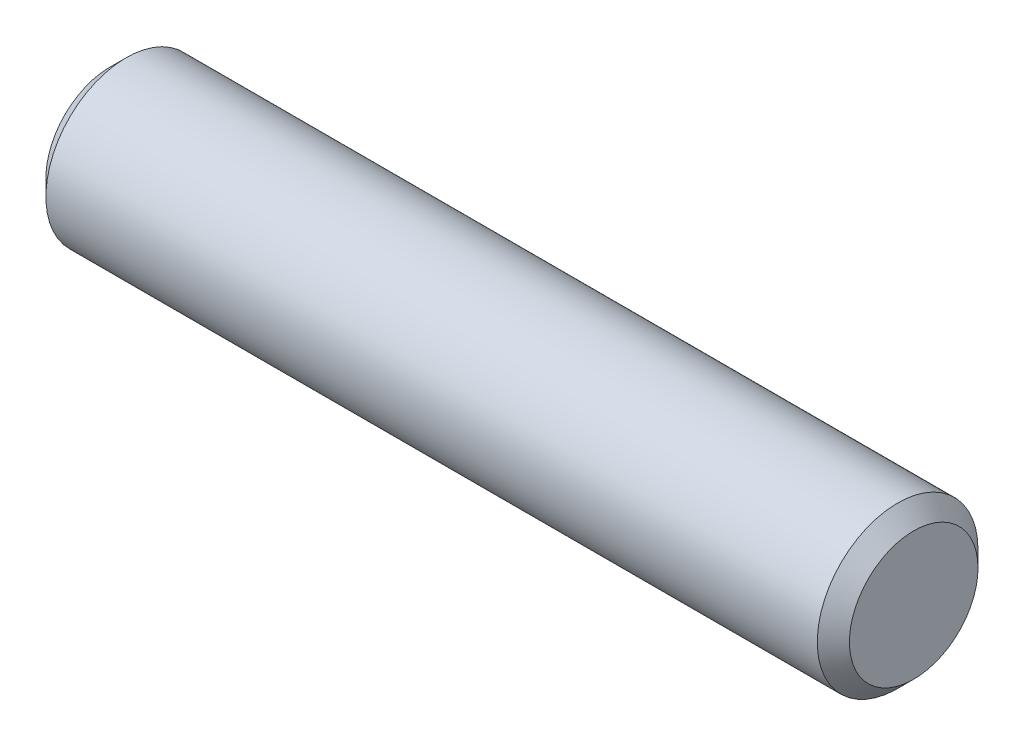
SolidWorks part; units mm, degrees
material "Alloy Steel"
ref_plane "Front" through (0, 0, 0) normal (0, 0, 1) x (1, 0, 0)
ref_plane "Top" through (0, 0, 0) normal (0, 1, 0) x (1, 0, 0)
ref_plane "Right" through (0, 0, 0) normal (1, 0, 0) x (0, 0, -1)
sketch "Sketch1" plane through (0, 0, 0) normal (0, 0, 1) x (1, 0, 0)
  line L0 (-7.9375, 0) -> (7.9375, 0) construction
  line L1 (7.9375, 1.5875) -> (7.9375, -1.5875) construction
  line L2 (-7.9375, 1.5875) -> (-7.9375, -1.5875) construction
  dimension "Length" = 15.875
  dimension "Diameter" = 3.175
sketch "Sketch2" plane through (0, 0, 0) normal (1, 0, 0) x (0, 0, -1)
  circle A0 centre (0, 0) radius 1.5875
extrude "Extrude1" add sketch "Sketch2" against normal up to vertex (7.9375 mm away) and the other way up to vertex (7.9375 mm away) up to point (-7.9375, 1.5875, 0) other way up to point (7.9375, 1.5875, 0)
chamfer "Chamfer1" distance 0.3175 angle 45 2 edges at (7.9375, 0, -1.5875) (-7.9375, 0, -1.5875)
equation "\"D1@Chamfer1\" = \"Diameter@Sketch1\"*.1"
